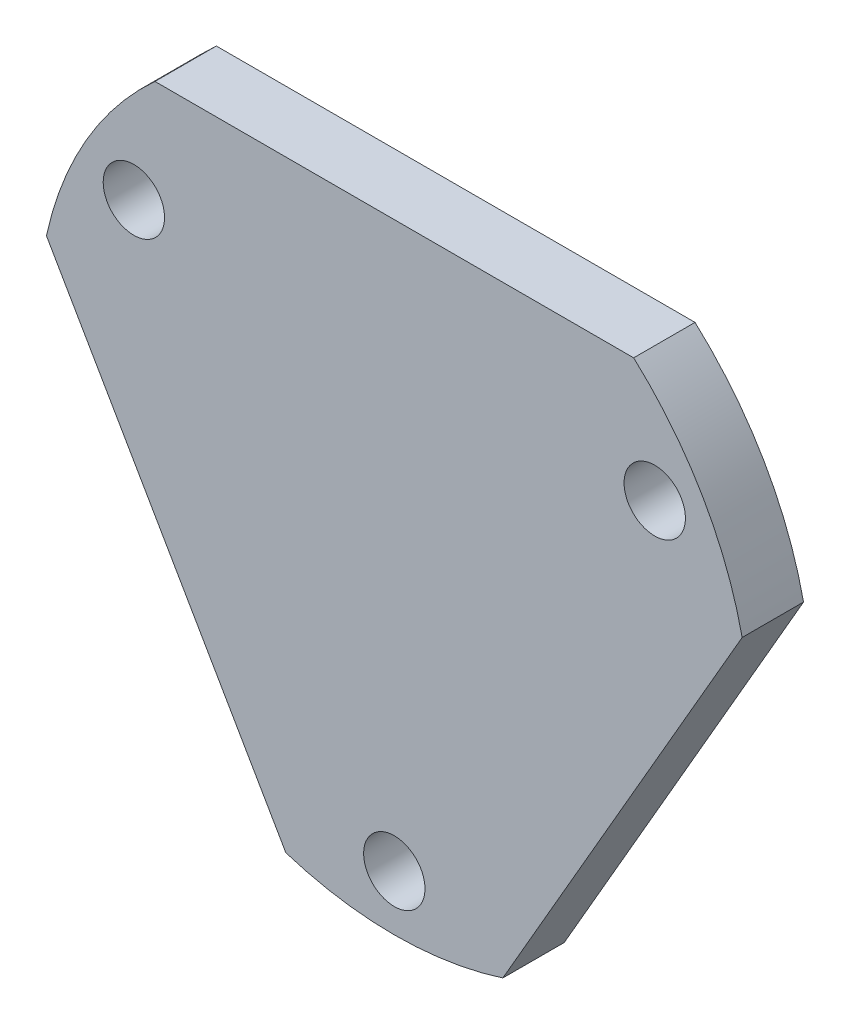
SolidWorks part; units mm, degrees
ref_plane "Front" through (0, 0, 0) normal (0, 0, 1) x (1, 0, 0)
ref_plane "Top" through (0, 0, 0) normal (0, 1, 0) x (1, 0, 0)
ref_plane "Right" through (0, 0, 0) normal (1, 0, 0) x (0, 0, -1)
sketch "Эскиз1" plane through (0, 0, 0) normal (0, 0, -1) x (1, 0, 0)
  line L0 (-9.75, -10.7325) -> (9.75, -10.7325)
  line L1 (0, 21.4651) -> (-18.5893, -10.7325) construction
  line L2 (-18.5893, -10.7325) -> (18.5893, -10.7325) construction
  line L3 (18.5893, -10.7325) -> (0, 21.4651) construction
  line L4 (-14.1697, -3.0775) -> (-4.4197, 13.81)
  line L5 (4.4197, 13.81) -> (14.1697, -3.0775)
  line L6 (7.0475, 14.5) -> (-2.501, 14.5) construction
  line L7 (7.0475, 13.5) -> (-2.501, 13.5) construction
  line L8 (0, 12.25) -> (0, 0) construction
  circle A0 centre (0, 0) radius 10.7325 construction
  circle A1 centre (0, 0) radius 14.5 construction
  circle A3 centre (0, 12.25) radius 1.25
  circle A5 centre (0, 0) radius 12.25 construction
  circle A6 centre (10.6088, -6.125) radius 1.25
  circle A7 centre (-10.6088, -6.125) radius 1.25
  arc A8 (-4.4197, 13.81) -> (4.4197, 13.81) centre (0, 0) cw
  arc A9 (14.1697, -3.0775) -> (9.75, -10.7325) centre (0, 0) cw
  arc A10 (-9.75, -10.7325) -> (-14.1697, -3.0775) centre (0, 0) cw
  point P7 (0, 0)
  point P10 (0, 0)
  point P11 (0, 0)
  point P12 (0, 0)
  point P13 (0, 0)
  point P27 (0, 0)
  dimension "D1" = 19.5
  dimension "D2" = 29
  dimension "D4" = 1
  dimension "D5" = 2.5
  dimension "D6" = 3
  dimension "D7" = 22.9825
  dimension "D3" = 21.4651
extrude "Бобышка-Вытянуть1" add sketch "Эскиз1" along normal blind 2.5
